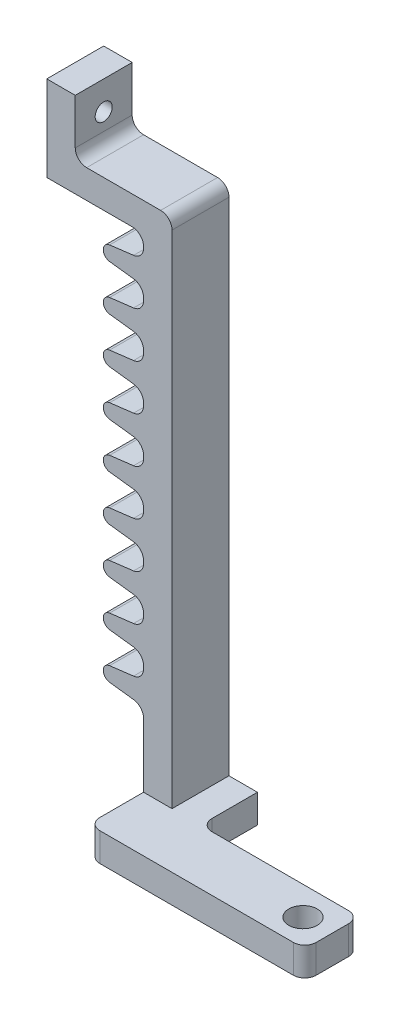
SolidWorks part; units mm, degrees
ref_plane "Front Plane" through (0, 0, 0) normal (0, 0, 1) x (1, 0, 0)
ref_plane "Top Plane" through (0, 0, 0) normal (0, 1, 0) x (1, 0, 0)
ref_plane "Right Plane" through (0, 0, 0) normal (1, 0, 0) x (0, 0, -1)
sketch "Sketch1" plane through (0, 0, 0) normal (0, 1, 0) x (1, 0, 0)
  line L0 (-8, 56.9408) -> (-8, 59.7408)
  line L1 (0, 57.5) -> (0, -57.5) construction
  line L2 (8, 56.9408) -> (8, 59.7408)
  line L3 (-6, 61.7408) -> (6, 61.7408)
  line L4 (39.4147, 47.8999) -> (47.8999, 39.4147)
  line L9 (34.6063, 45.9201) -> (36.5862, 47.8999)
  line L10 (45.9201, 34.6063) -> (47.8999, 36.5862)
  line L15 (61.7408, 6) -> (61.7408, -6)
  line L16 (56.9408, 8) -> (59.7408, 8)
  line L17 (56.9408, -8) -> (59.7408, -8)
  line L22 (47.8999, -39.4147) -> (39.4147, -47.8999)
  line L23 (45.9201, -34.6063) -> (47.8999, -36.5862)
  line L24 (34.6063, -45.9201) -> (36.5862, -47.8999)
  line L29 (6, -61.7408) -> (-6, -61.7408)
  line L30 (8, -56.9408) -> (8, -59.7408)
  line L31 (-8, -56.9408) -> (-8, -59.7408)
  line L36 (-39.4147, -47.8999) -> (-47.8999, -39.4147)
  line L37 (-34.6063, -45.9201) -> (-36.5862, -47.8999)
  line L38 (-45.9201, -34.6063) -> (-47.8999, -36.5862)
  line L43 (-61.7408, -6) -> (-61.7408, 6)
  line L44 (-56.9408, -8) -> (-59.7408, -8)
  line L45 (-56.9408, 8) -> (-59.7408, 8)
  line L50 (-47.8999, 39.4147) -> (-39.4147, 47.8999)
  line L51 (-45.9201, 34.6063) -> (-47.8999, 36.5862)
  line L52 (-34.6063, 45.9201) -> (-36.5862, 47.8999)
  arc A0 (-8, 56.9408) -> (-34.6063, 45.9201) centre (0, 0) ccw
  arc A1 (6, 61.7408) -> (8, 59.7408) centre (6, 59.7408) cw
  arc A2 (-6, 61.7408) -> (-8, 59.7408) centre (-6, 59.7408) ccw
  arc A3 (39.4147, 47.8999) -> (36.5862, 47.8999) centre (38.0005, 46.4857) ccw
  arc A4 (47.8999, 39.4147) -> (47.8999, 36.5862) centre (46.4857, 38.0005) cw
  arc A5 (61.7408, 6) -> (59.7408, 8) centre (59.7408, 6) ccw
  arc A6 (61.7408, -6) -> (59.7408, -8) centre (59.7408, -6) cw
  arc A7 (47.8999, -39.4147) -> (47.8999, -36.5862) centre (46.4857, -38.0005) ccw
  arc A8 (39.4147, -47.8999) -> (36.5862, -47.8999) centre (38.0005, -46.4857) cw
  arc A9 (6, -61.7408) -> (8, -59.7408) centre (6, -59.7408) ccw
  arc A10 (-6, -61.7408) -> (-8, -59.7408) centre (-6, -59.7408) cw
  arc A11 (-39.4147, -47.8999) -> (-36.5862, -47.8999) centre (-38.0005, -46.4857) ccw
  arc A12 (-47.8999, -39.4147) -> (-47.8999, -36.5862) centre (-46.4857, -38.0005) cw
  arc A13 (-61.7408, -6) -> (-59.7408, -8) centre (-59.7408, -6) ccw
  arc A14 (-61.7408, 6) -> (-59.7408, 8) centre (-59.7408, 6) cw
  arc A15 (-47.8999, 39.4147) -> (-47.8999, 36.5862) centre (-46.4857, 38.0005) ccw
  arc A16 (-39.4147, 47.8999) -> (-36.5862, 47.8999) centre (-38.0005, 46.4857) cw
  arc A17 (-45.9201, 34.6063) -> (-56.9408, 8) centre (0, 0) ccw
  arc A18 (-56.9408, -8) -> (-45.9201, -34.6063) centre (0, 0) ccw
  arc A19 (34.6063, 45.9201) -> (8, 56.9408) centre (0, 0) ccw
  arc A20 (-34.6063, -45.9201) -> (-8, -56.9408) centre (0, 0) ccw
  arc A21 (8, -56.9408) -> (34.6063, -45.9201) centre (0, 0) ccw
  arc A22 (45.9201, -34.6063) -> (56.9408, -8) centre (0, 0) ccw
  arc A23 (56.9408, 8) -> (45.9201, 34.6063) centre (0, 0) ccw
  point P11 (8, 61.7408)
  point P14 (-8, 61.7408)
  point P17 (-8, 58.3408)
  point P98 (0, 0)
  dimension "D1" = 115
  dimension "D2" = 2
  dimension "D3" = 16
  dimension "D4" = 2.8
  dimension "D7" = 8
extrude "Boss-Extrude1" add sketch "Sketch1" along normal blind 7
sketch "Sketch2" plane through (0, 7, 0) normal (0, 1, 0) x (1, 0, 0)
  line L0 (-57.5, 0) -> (57.5, 0) construction
  line L1 (0, 0) -> (0, 10) construction
  line L7 (17, 5) -> (22, 5)
  line L14 (0, 10) -> (29.7122, 10) construction
  line L15 (0, 10) -> (-19.5, 10) construction
  line L17 (17, 5) -> (17, 15)
  line L18 (-22, 15) -> (-17, 15)
  line L19 (-22, 15) -> (-22, 5)
  line L20 (-22, 5) -> (-17, 5)
  line L21 (-17, 15) -> (-17, 5)
  line L22 (-22, 15) -> (-17, 5) construction
  line L23 (-22, 5) -> (-17, 15) construction
  line L24 (17, 15) -> (22, 15)
  line L25 (22, 5) -> (22, 15)
  line L26 (17, 5) -> (22, 15) construction
  line L27 (17, 15) -> (22, 5) construction
  circle A0 centre (0, 0) radius 57.5 construction
  point P8 (19.5, 10)
  dimension "D1" = 10
  dimension "D2" = 17
  dimension "D3" = 17
  dimension "D4" = 10
  dimension "D5" = 5
  dimension "D6" = 10
  dimension "D7" = 5
extrude "Boss-Extrude2" add sketch "Sketch2" along normal blind 95
sketch "Sketch15" plane through (0, 0, 0) normal (0, -1, 0) x (1, 0, 0)
  circle A0 centre (0, 0) radius 3.5
  dimension "D1" = 7
extrude "Cut-Extrude3" cut sketch "Sketch15" along direction (0, 1, 0) on the side against the normal up to surface (7 mm away) contours A0 up to face at (0, 7, 0)
sketch "Sketch16" plane through (0, 0, 0) normal (0, -1, 0) x (1, 0, 0)
  line L1 (-6, 59.8) -> (6, 59.8)
  line L2 (-6, 59.8) -> (-6, 57.5)
  line L3 (-6, 57.5) -> (6, 57.5)
  line L4 (6, 59.8) -> (6, 57.5)
  point P5 (0, 57.5)
  dimension "D1" = 2.3
  dimension "D2" = 12
  dimension "D3" = 57.5
sketch "Sketch17" plane through (0, 7, 0) normal (0, 1, 0) x (1, 0, 0)
  line L0 (-6, -57.5) -> (6, -57.5) construction
  line L1 (-6, -57.5) -> (6, -57.5)
  line L2 (-6, -57.5) -> (-6, -60.5)
  line L3 (-6, -60.5) -> (6, -60.5)
  line L4 (6, -60.5) -> (6, -57.5)
  dimension "D1" = 3
ref_axis "Axis1" through (0, 107.1, 0) along (0, -1, 0)
sketch "Sketch18" plane through (-17, 0, 0) normal (1, 0, 0) x (0, 0, -1)
  line L0 (15, 102) -> (15, 7) construction
  line L1 (5, 102) -> (15, 102)
  line L2 (5, 102) -> (5, 97)
  line L3 (5, 97) -> (15, 97)
  line L4 (15, 102) -> (15, 97)
  dimension "D1" = 5
extrude "Boss-Extrude3" add sketch "Sketch18" along normal up to surface (34 mm away) up to face at (17, 54.5, -10)
sketch "Sketch19" plane through (0, 0, -15) normal (0, 0, -1) x (-1, 0, 0)
  line L0 (-17, 93) -> (-11.0447, 92.2688)
  line L1 (-17, 97) -> (-17, 7) construction
  line L4 (-11, 91) -> (-19.8185, 91) construction
  line L5 (-17, 89) -> (-11.0447, 89.7312)
  line L6 (-17, 93) -> (-17, 89)
  arc A1 (-11.0447, 92.2688) -> (-11.0447, 89.7312) centre (-11.2005, 91) cw
  dimension "D1" = 6
  dimension "D4" = 4
  dimension "D2" = 7
  dimension "D3" = 4
extrude "Boss-Extrude4" add sketch "Sketch19" against normal blind 10
fillet "Fillet1" radius 2 2 edges at (17, 93, -10) (17, 89, -10)
fillet "Fillet2" radius 2 4 edges at (-22, 102, -10) (22, 102, -10) (-17, 97, -10) (17, 97, -10)
pattern_linear "LPattern2" count 9 spacing 8 along (0, -1, 0) of "Fillet1", "Boss-Extrude4"
sketch "Sketch20" plane through (0, 7, 0) normal (0, 1, 0) x (1, 0, 0)
  line L0 (0, 0) -> (0, 50) construction
  circle A0 centre (0, 50) radius 2.5
  dimension "D2" = 5
  dimension "D1" = 50
extrude "Cut-Extrude4" cut sketch "Sketch20" against normal blind 10
pattern_circular "CirPattern2" count 4 over 360 about axis through (0, 107.1, 0) along (0, -1, 0) of "Cut-Extrude4"
sketch "Sketch22" plane through (0, 0, 0) normal (1, 0, 0) x (0, 0, -1)
  line L1 (67.7074, 106.8544) -> (-67.9721, 106.8544)
  line L2 (67.7074, 106.8544) -> (67.7074, -6.1109)
  line L3 (67.7074, -6.1109) -> (-67.9721, -6.1109)
  line L4 (-67.9721, 106.8544) -> (-67.9721, -6.1109)
  dimension "D1" = 67.7074
  dimension "D2" = 112.9653
  dimension "D3" = 106.8544
  dimension "D4" = 67.9721
extrude "Cut-Extrude5" cut sketch "Sketch22" against normal up to surface (61.7408 mm away) up to face at (-61.7408, 3.5, 0)
sketch "Sketch23" plane through (0, 7, 0) normal (0, 1, 0) x (1, 0, 0)
  line L1 (17, 5) -> (53, 5)
  line L2 (17, 5) -> (17, -2.6871)
  line L3 (19, -4.6871) -> (53, -4.6871)
  line L4 (55, 3) -> (55, -2.6871)
  line L29 (6, 61.7408) -> (0, 61.7408)
  line L30 (0, 61.7408) -> (0, 52.5)
  line L35 (0, 47.5) -> (0, 3.5)
  line L36 (0, -3.5) -> (0, -47.5)
  line L37 (0, -52.5) -> (0, -61.7408)
  line L42 (0, -61.7408) -> (6, -61.7408)
  line L43 (8, -59.7408) -> (8, -56.9408)
  line L44 (34.6063, -45.9201) -> (36.5862, -47.8999)
  line L45 (39.4147, -47.8999) -> (47.8999, -39.4147)
  line L46 (47.8999, -36.5862) -> (45.9201, -34.6063)
  line L47 (56.9408, -8) -> (59.7408, -8)
  line L48 (61.7408, -6) -> (61.7408, 6)
  line L49 (59.7408, 8) -> (56.9408, 8)
  line L50 (45.9201, 34.6063) -> (47.8999, 36.5862)
  line L51 (47.8999, 39.4147) -> (39.4147, 47.8999)
  line L52 (36.5862, 47.8999) -> (34.6063, 45.9201)
  line L53 (8, 56.9408) -> (8, 59.7408)
  line L54 (6, 61.7408) -> (0, 61.7408)
  line L55 (0, 61.7408) -> (0, 52.5)
  line L60 (0, 47.5) -> (0, 3.5)
  line L61 (0, -3.5) -> (0, -47.5)
  line L62 (0, -52.5) -> (0, -61.7408)
  line L67 (0, -61.7408) -> (6, -61.7408)
  line L68 (8, -59.7408) -> (8, -56.9408)
  line L69 (34.6063, -45.9201) -> (36.5862, -47.8999)
  line L70 (39.4147, -47.8999) -> (47.8999, -39.4147)
  line L71 (47.8999, -36.5862) -> (45.9201, -34.6063)
  line L72 (56.9408, -8) -> (59.7408, -8)
  line L73 (61.7408, -6) -> (61.7408, 6)
  line L74 (59.7408, 8) -> (56.9408, 8)
  line L75 (45.9201, 34.6063) -> (47.8999, 36.5862)
  line L76 (47.8999, 39.4147) -> (39.4147, 47.8999)
  line L77 (36.5862, 47.8999) -> (34.6063, 45.9201)
  line L78 (8, 56.9408) -> (8, 59.7408)
  arc A0 (19, -4.6871) -> (17, -2.6871) centre (19, -2.6871) cw
  arc A1 (53, -4.6871) -> (55, -2.6871) centre (53, -2.6871) ccw
  arc A2 (55, 3) -> (53, 5) centre (53, 3) ccw
  circle A3 centre (50, 0) radius 2.5 construction
  circle A4 centre (50, 0) radius 2.5
  arc A18 (0, 47.5) -> (0, 52.5) centre (0, 50) ccw
  arc A19 (0, -3.5) -> (0, 3.5) centre (0, 0) ccw
  arc A20 (0, -52.5) -> (0, -47.5) centre (0, -50) ccw
  arc A21 (6, -61.7408) -> (8, -59.7408) centre (6, -59.7408) ccw
  arc A22 (8, -56.9408) -> (34.6063, -45.9201) centre (0, 0) ccw
  arc A23 (36.5862, -47.8999) -> (39.4147, -47.8999) centre (38.0005, -46.4857) ccw
  arc A24 (47.8999, -39.4147) -> (47.8999, -36.5862) centre (46.4857, -38.0005) ccw
  arc A25 (45.9201, -34.6063) -> (56.9408, -8) centre (0, 0) ccw
  arc A26 (59.7408, -8) -> (61.7408, -6) centre (59.7408, -6) ccw
  arc A27 (61.7408, 6) -> (59.7408, 8) centre (59.7408, 6) ccw
  arc A28 (56.9408, 8) -> (45.9201, 34.6063) centre (0, 0) ccw
  arc A29 (47.8999, 36.5862) -> (47.8999, 39.4147) centre (46.4857, 38.0005) ccw
  arc A30 (39.4147, 47.8999) -> (36.5862, 47.8999) centre (38.0005, 46.4857) ccw
  arc A31 (34.6063, 45.9201) -> (8, 56.9408) centre (0, 0) ccw
  arc A32 (8, 59.7408) -> (6, 61.7408) centre (6, 59.7408) ccw
  arc A33 (0, 47.5) -> (0, 52.5) centre (0, 50) ccw
  arc A34 (0, -3.5) -> (0, 3.5) centre (0, 0) ccw
  arc A35 (0, -52.5) -> (0, -47.5) centre (0, -50) ccw
  arc A36 (6, -61.7408) -> (8, -59.7408) centre (6, -59.7408) ccw
  arc A37 (8, -56.9408) -> (34.6063, -45.9201) centre (0, 0) ccw
  arc A38 (36.5862, -47.8999) -> (39.4147, -47.8999) centre (38.0005, -46.4857) ccw
  arc A39 (47.8999, -39.4147) -> (47.8999, -36.5862) centre (46.4857, -38.0005) ccw
  arc A40 (45.9201, -34.6063) -> (56.9408, -8) centre (0, 0) ccw
  arc A41 (59.7408, -8) -> (61.7408, -6) centre (59.7408, -6) ccw
  arc A42 (61.7408, 6) -> (59.7408, 8) centre (59.7408, 6) ccw
  arc A43 (56.9408, 8) -> (45.9201, 34.6063) centre (0, 0) ccw
  arc A44 (47.8999, 36.5862) -> (47.8999, 39.4147) centre (46.4857, 38.0005) ccw
  arc A45 (39.4147, 47.8999) -> (36.5862, 47.8999) centre (38.0005, 46.4857) ccw
  arc A46 (34.6063, 45.9201) -> (8, 56.9408) centre (0, 0) ccw
  arc A47 (8, 59.7408) -> (6, 61.7408) centre (6, 59.7408) ccw
  point P0 (55.5353, -4.6871)
  point P7 (17, -4.6871)
  point P11 (55, -4.6871)
  dimension "D3" = 2
  dimension "D1" = 38
  dimension "D2" = 9.6871
  dimension "D4" = 0
extrude "Boss-Extrude5" add sketch "Sketch23" along normal blind 5 contours L4 A2 L1 L2 A0 L3 A1 A4 region at (35.1593, 7, -0.1762)
sketch "Sketch26" plane through (0, 7, 0) normal (0, 1, 0) x (1, 0, 0)
  line L25 (6, 61.7408) -> (0, 61.7408)
  line L26 (0, 61.7408) -> (0, 52.5)
  line L31 (0, 47.5) -> (0, 3.5)
  line L32 (0, -3.5) -> (0, -47.5)
  line L33 (0, -52.5) -> (0, -61.7408)
  line L38 (0, -61.7408) -> (6, -61.7408)
  line L39 (8, -59.7408) -> (8, -56.9408)
  line L40 (34.6063, -45.9201) -> (36.5862, -47.8999)
  line L41 (39.4147, -47.8999) -> (47.8999, -39.4147)
  line L42 (47.8999, -36.5862) -> (45.9201, -34.6063)
  line L43 (56.9408, -8) -> (59.7408, -8)
  line L44 (61.7408, -6) -> (61.7408, 6)
  line L45 (59.7408, 8) -> (56.9408, 8)
  line L46 (45.9201, 34.6063) -> (47.8999, 36.5862)
  line L47 (47.8999, 39.4147) -> (39.4147, 47.8999)
  line L48 (36.5862, 47.8999) -> (34.6063, 45.9201)
  line L49 (8, 56.9408) -> (8, 59.7408)
  line L50 (6, 61.7408) -> (0, 61.7408)
  line L51 (0, 61.7408) -> (0, 52.5)
  line L56 (0, 47.5) -> (0, 3.5)
  line L57 (0, -3.5) -> (0, -47.5)
  line L58 (0, -52.5) -> (0, -61.7408)
  line L63 (0, -61.7408) -> (6, -61.7408)
  line L64 (8, -59.7408) -> (8, -56.9408)
  line L65 (34.6063, -45.9201) -> (36.5862, -47.8999)
  line L66 (39.4147, -47.8999) -> (47.8999, -39.4147)
  line L67 (47.8999, -36.5862) -> (45.9201, -34.6063)
  line L68 (56.9408, -8) -> (59.7408, -8)
  line L69 (61.7408, -6) -> (61.7408, 6)
  line L70 (59.7408, 8) -> (56.9408, 8)
  line L71 (45.9201, 34.6063) -> (47.8999, 36.5862)
  line L72 (47.8999, 39.4147) -> (39.4147, 47.8999)
  line L73 (36.5862, 47.8999) -> (34.6063, 45.9201)
  line L74 (8, 56.9408) -> (8, 59.7408)
  arc A15 (0, 47.5) -> (0, 52.5) centre (0, 50) ccw
  arc A16 (0, -3.5) -> (0, 3.5) centre (0, 0) ccw
  arc A17 (0, -52.5) -> (0, -47.5) centre (0, -50) ccw
  arc A18 (6, -61.7408) -> (8, -59.7408) centre (6, -59.7408) ccw
  arc A19 (8, -56.9408) -> (34.6063, -45.9201) centre (0, 0) ccw
  arc A20 (36.5862, -47.8999) -> (39.4147, -47.8999) centre (38.0005, -46.4857) ccw
  arc A21 (47.8999, -39.4147) -> (47.8999, -36.5862) centre (46.4857, -38.0005) ccw
  arc A22 (45.9201, -34.6063) -> (56.9408, -8) centre (0, 0) ccw
  arc A23 (59.7408, -8) -> (61.7408, -6) centre (59.7408, -6) ccw
  arc A24 (61.7408, 6) -> (59.7408, 8) centre (59.7408, 6) ccw
  arc A25 (56.9408, 8) -> (45.9201, 34.6063) centre (0, 0) ccw
  arc A26 (47.8999, 36.5862) -> (47.8999, 39.4147) centre (46.4857, 38.0005) ccw
  arc A27 (39.4147, 47.8999) -> (36.5862, 47.8999) centre (38.0005, 46.4857) ccw
  arc A28 (34.6063, 45.9201) -> (8, 56.9408) centre (0, 0) ccw
  arc A29 (8, 59.7408) -> (6, 61.7408) centre (6, 59.7408) ccw
  arc A30 (0, 47.5) -> (0, 52.5) centre (0, 50) ccw
  arc A31 (0, -3.5) -> (0, 3.5) centre (0, 0) ccw
  arc A32 (0, -52.5) -> (0, -47.5) centre (0, -50) ccw
  arc A33 (6, -61.7408) -> (8, -59.7408) centre (6, -59.7408) ccw
  arc A34 (8, -56.9408) -> (34.6063, -45.9201) centre (0, 0) ccw
  arc A35 (36.5862, -47.8999) -> (39.4147, -47.8999) centre (38.0005, -46.4857) ccw
  arc A36 (47.8999, -39.4147) -> (47.8999, -36.5862) centre (46.4857, -38.0005) ccw
  arc A37 (45.9201, -34.6063) -> (56.9408, -8) centre (0, 0) ccw
  arc A38 (59.7408, -8) -> (61.7408, -6) centre (59.7408, -6) ccw
  arc A39 (61.7408, 6) -> (59.7408, 8) centre (59.7408, 6) ccw
  arc A40 (56.9408, 8) -> (45.9201, 34.6063) centre (0, 0) ccw
  arc A41 (47.8999, 36.5862) -> (47.8999, 39.4147) centre (46.4857, 38.0005) ccw
  arc A42 (39.4147, 47.8999) -> (36.5862, 47.8999) centre (38.0005, 46.4857) ccw
  arc A43 (34.6063, 45.9201) -> (8, 56.9408) centre (0, 0) ccw
  arc A44 (8, 59.7408) -> (6, 61.7408) centre (6, 59.7408) ccw
  dimension "D1" = 0
extrude "Cut-Extrude6" cut sketch "Sketch26" against normal blind 10
sketch "Sketch27" plane through (22, 0, 0) normal (1, 0, 0) x (0, 0, -1)
  line L0 (15, 100) -> (15, 7) construction
  line L1 (5, 7) -> (15, 7)
  line L2 (5, 7) -> (5, 12)
  line L3 (5, 12) -> (15, 12)
  line L4 (15, 7) -> (15, 12)
  point P7 (0, 0)
extrude "Boss-Extrude6" add sketch "Sketch27" along normal blind 5
sketch "Sketch28" plane through (0, 102, 0) normal (0, 1, 0) x (1, 0, 0)
  line L0 (0, 5) -> (20, 5) construction
  line L1 (0, 15) -> (5, 15)
  line L2 (0, 15) -> (0, 5)
  line L3 (0, 5) -> (5, 5)
  line L4 (5, 15) -> (5, 5)
  dimension "D1" = 5
extrude "Boss-Extrude7" add sketch "Sketch28" along normal blind 10
sketch "Sketch29" plane through (5, 0, 0) normal (1, 0, 0) x (0, 0, -1)
  line L0 (5, 112) -> (15, 102) construction
  circle A0 centre (10, 107) radius 1.5
  dimension "D1" = 3
extrude "Cut-Extrude7" cut sketch "Sketch29" against normal up to surface (5 mm away) up to face at (0, 104.5, -10)
fillet "Fillet3" radius 2 2 edges at (27, 9.5, -5) (5, 102, -10)
equation "\"85.00.00mm\"=8500"
